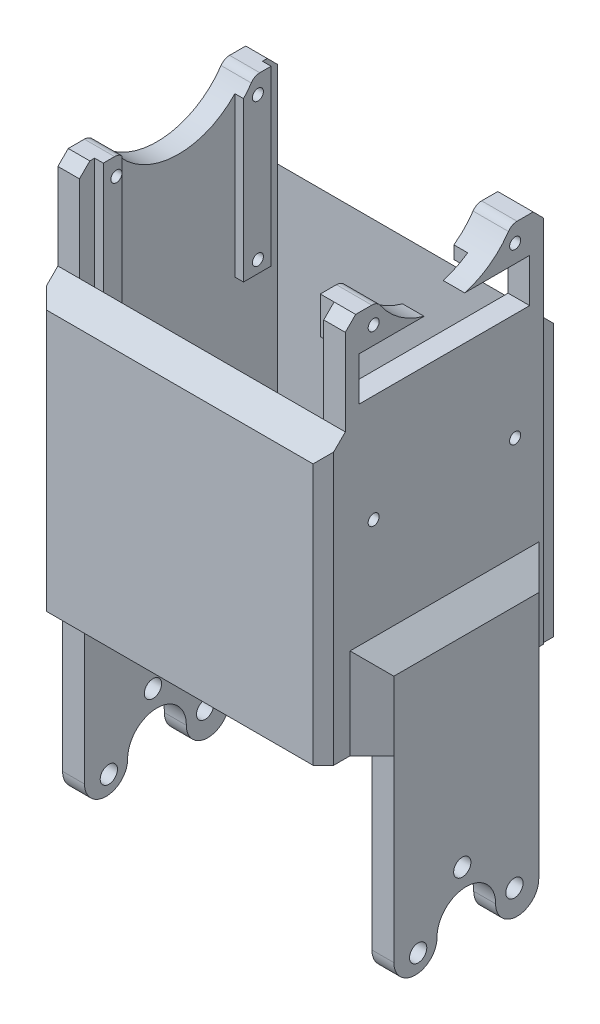
SolidWorks part; units mm, degrees
material "PLA"
ref_plane "Front Plane" through (0, 0, 0) normal (0, 0, 1) x (1, 0, 0)
ref_plane "Top Plane" through (0, 0, 0) normal (0, 1, 0) x (1, 0, 0)
ref_plane "Right Plane" through (0, 0, 0) normal (1, 0, 0) x (0, 0, -1)
sketch "Sketch1" plane through (0, 0, 0) normal (0, 0, 1) x (1, 0, 0)
  line L0 (0, 0) -> (35.4, 0)
  line L1 (35.4, 0) -> (35.4, 51.875)
  line L2 (0, 0) -> (-3.125, 0) construction
  line L3 (35.4, 0) -> (38.525, 0) construction
  line L4 (-3.125, -3.125) -> (38.525, -3.125)
  line L5 (38.525, -3.125) -> (38.525, 51.875)
  line L6 (-3.125, -3.125) -> (-3.125, 51.875)
  line L7 (0, 0) -> (0, 51.875)
  line L8 (0, 51.875) -> (-3.125, 51.875)
  line L9 (35.4, 51.875) -> (38.525, 51.875)
  dimension "D1" = 35.4
  dimension "D2" = 3.125
  dimension "D3" = 3.125
  dimension "D4" = 3.125
  dimension "D5" = 55
  dimension "D6" = 55
extrude "Boss-Extrude1" add sketch "Sketch1" along normal blind 28.72
sketch "Sketch2" plane through (38.525, 0, 0) normal (1, 0, 0) x (0, 0, -1)
  line L0 (-28.72, 46.285) -> (0, 46.285) construction
  line L1 (-28.72, -3.125) -> (-28.72, 51.875) construction
  line L2 (0, -3.125) -> (0, 51.875) construction
  line L3 (-28.72, 51.875) -> (0, 51.875) construction
  line L4 (-14.36, 46.285) -> (-14.36, 57.485) construction
  circle A0 centre (-14.36, 57.485) radius 11.2
  dimension "D1" = 5.59
  dimension "D2" = 11.2
extrude "Cut-Extrude1" cut sketch "Sketch2" against normal through all
fillet "Fillet2" radius 1.5 4 edges at (-1.5625, 51.875, 24.0537) (-1.5625, 51.875, 4.6663) (36.9625, 51.875, 4.6663) (36.9625, 51.875, 24.0537)
sketch "Sketch3" plane through (0, 0, 0) normal (0, 0, -1) x (-1, 0, 0)
  line L1 (-38.325, 37.875) -> (3.125, 37.875)
  line L2 (-38.325, 37.875) -> (-38.325, -3.125)
  line L3 (-38.325, -3.125) -> (3.125, -3.125)
  line L4 (3.125, 37.875) -> (3.125, -3.125)
extrude "Boss-Extrude2" add sketch "Sketch3" along normal blind 3.175
sketch "Sketch4" plane through (0, 0, 28.72) normal (0, 0, 1) x (1, 0, 0)
  line L1 (-3.125, 37.875) -> (38.525, 37.875)
  line L2 (-3.125, 37.875) -> (-3.125, -3.125)
  line L3 (-3.125, -3.125) -> (38.525, -3.125)
  line L4 (38.525, 37.875) -> (38.525, -3.125)
extrude "Boss-Extrude3" add sketch "Sketch4" along normal blind 3.175
chamfer "Chamfer1" distance 3.175 angle 45 2 edges at (17.6, 37.875, -3.175) (17.7, 37.875, 31.895)
chamfer "Chamfer2" distance 1.5 angle 45 4 edges at (-1.5625, 51.875, 0) (36.9625, 51.875, 0) (-1.5625, 51.875, 28.72) (36.9625, 51.875, 28.72)
chamfer "Chamfer3" distance 1.5 angle 45 4 edges at (-3.125, 15.7875, -3.175) (38.325, 15.7875, -3.175) (38.525, 15.7875, 31.895) (-3.125, 15.7875, 31.895)
sketch "Sketch5" plane through (0, 0, 0) normal (1, 0, 0) x (0, 0, -1)
  line L0 (-3.8368, 51.875) -> (-1.5, 51.875) construction
  line L2 (-2.2006, 51.875) -> (-2.2006, 26.7908)
  line L3 (-2.2006, 26.7908) -> (-6.2006, 26.7908)
  line L4 (-6.2006, 49.8127) -> (-6.2006, 26.7908)
  line L6 (-26.5194, 51.875) -> (-26.5194, 26.7908)
  line L7 (-26.5194, 26.7908) -> (-23.7797, 26.7908)
  line L8 (-23.7797, 51.4262) -> (-23.7797, 26.7908)
  line L9 (-27.22, 51.875) -> (-24.8832, 51.875) construction
  line L10 (-3.8368, 51.875) -> (-2.2006, 51.875)
  line L11 (-26.5194, 51.875) -> (-24.8832, 51.875)
  circle A0 centre (-24.61, 49.2608) radius 0.8
  circle A1 centre (-24.61, 28.5608) radius 0.8
  circle A2 centre (-4.11, 28.5608) radius 0.8
  circle A3 centre (-4.11, 49.2608) radius 0.8
  arc A4 (-3.8368, 51.875) -> (-5.0797, 51.2148) centre (-3.8368, 50.375) ccw construction
  arc A5 (-23.6403, 51.2148) -> (-5.0797, 51.2148) centre (-14.36, 57.485) ccw construction
  arc A6 (-23.6403, 51.2148) -> (-24.8832, 51.875) centre (-24.8832, 50.375) ccw construction
  arc A7 (-3.8368, 51.875) -> (-5.0797, 51.2148) centre (-3.8368, 50.375) ccw
  arc A8 (-23.6403, 51.2148) -> (-23.7797, 51.4262) centre (-14.36, 57.485) ccw
  arc A9 (-23.6403, 51.2148) -> (-24.8832, 51.875) centre (-24.8832, 50.375) ccw
  arc A10 (-6.2006, 49.8127) -> (-5.0797, 51.2148) centre (-14.36, 57.485) ccw
  line M8 (-1.5, 51.875) -> (-3.8368, 51.875)
  arc M9 (-3.8368, 51.875) -> (-5.0797, 51.2148) centre (-3.8368, 50.375) ccw
  arc M10 (-5.0797, 51.2148) -> (-23.6403, 51.2148) centre (-14.36, 57.485) cw
  arc M11 (-23.6403, 51.2148) -> (-24.8832, 51.875) centre (-24.8832, 50.375) ccw
  line M12 (-24.8832, 51.875) -> (-27.22, 51.875)
extrude "Boss-Extrude4" add sketch "Sketch5" along normal blind 1.25 contours L4 L3 L2 A3 A2 M10 M8 M9 | L8 L6 L7 A1 A0 M11 M12 region at (0, 39.3275, 25.186) region at (0, 39.1233, 4.1775)
sketch "Sketch6" plane through (0, 0, 0) normal (1, 0, 0) x (0, 0, -1)
  circle A0 centre (-24.61, 49.2608) radius 0.8
  circle A1 centre (-24.61, 28.5608) radius 0.8
  circle A2 centre (-4.11, 28.5608) radius 0.8
  circle A3 centre (-4.11, 49.2608) radius 0.8
extrude "Cut-Extrude2" cut sketch "Sketch6" against normal up to next
sketch "Sketch7" plane through (0, -3.125, 0) normal (0, -1, 0) x (1, 0, 0)
  line L0 (11.7, 22.36) -> (23.7, 22.36) construction
  line L1 (23.7, 22.36) -> (23.7, 6.36) construction
  line L2 (23.7, 6.36) -> (11.7, 6.36) construction
  line L3 (11.7, 6.36) -> (11.7, 22.36) construction
  line L6 (-3.125, 30.395) -> (-3.125, -1.675) construction
  line L7 (-1.625, 31.895) -> (37.025, 31.895) construction
  circle A0 centre (11.7, 22.36) radius 1.35
  circle A1 centre (23.7, 22.36) radius 1.35
  circle A2 centre (23.7, 6.36) radius 1.35
  circle A3 centre (11.7, 6.36) radius 1.35
  dimension "D1" = 2.7
  dimension "D2" = 2.7
  dimension "D3" = 2.7
  dimension "D4" = 2.7
  dimension "D5" = 14.825
  dimension "D6" = 9.535
extrude "Cut-Extrude3" cut sketch "Sketch7" against normal up to next
sketch "Sketch8" plane through (35.4, 0, 0) normal (-1, 0, 0) x (0, 0, 1)
  line L0 (7.86, 48.7133) -> (7.86, 45.9108) construction
  line L1 (1.5, 51.875) -> (5.0709, 51.875)
  line L2 (1.5, 51.875) -> (1.5, 46.5164)
  line L3 (1.5, 46.5164) -> (7.86, 46.5164)
  line L4 (7.86, 48.7133) -> (7.86, 46.5164)
  line L5 (20.86, 45.9108) -> (20.86, 48.7133) construction
  line L6 (20.86, 46.5164) -> (27.22, 46.5164)
  line L7 (20.86, 46.5164) -> (20.86, 48.7133)
  line L8 (23.6491, 51.875) -> (27.22, 51.875)
  line L9 (27.22, 46.5164) -> (27.22, 51.875)
  line L10 (28.72, 0) -> (28.72, 37.875) construction
  line L11 (28.72, 27.0608) -> (0, 27.0608)
  line L12 (28.72, 27.0608) -> (28.72, 22.5608)
  line L13 (28.72, 22.5608) -> (0, 22.5608)
  line L14 (0, 27.0608) -> (0, 22.5608)
  circle A0 centre (24.61, 49.2608) radius 0.8
  circle A1 centre (4.11, 49.2608) radius 0.8
  circle A2 centre (4.11, 24.8108) radius 0.8
  circle A3 centre (24.61, 24.735) radius 0.8758
  arc A4 (5.0077, 51.9796) -> (7.7768, 48.8846) centre (14.36, 57.5608) ccw construction
  arc A5 (5.0709, 51.875) -> (7.7768, 48.8846) centre (14.36, 57.5608) ccw
  arc A6 (20.9432, 48.8846) -> (23.7123, 51.9796) centre (14.36, 57.5608) ccw construction
  arc A7 (20.9432, 48.8846) -> (23.6491, 51.875) centre (14.36, 57.5608) ccw
  spline S0 degree 3 poles (-1990.0282, 140.523) (-63.2874, 38.9164) (7.1505, 51.8916) (8.5344, 45.7425) (-54.2619, 48.1267) (797.0615, -1788.4088) knots -94.086847 -94.086847 -94.086847 -94.086847 0.333333 0.666667 91.791331 91.791331 91.791331 91.791331 weights 1 1 1 1 1 1 only from (7.8374, 48.8108) to (7.86, 48.7133) construction
  spline S1 degree 3 poles (-490.8158, 1985.2839) (-30.2177, -10.261) (5.7924, 51.2853) (9.6673, 46.6143) (-37.1403, 7.4582) (460.9115, -1898.6662) knots -96.396237 -96.396237 -96.396237 -96.396237 0.333333 0.666667 89.616596 89.616596 89.616596 89.616596 weights 1 1 1 1 1 1 only from (7.7768, 48.8846) to (7.8374, 48.8108) construction
  spline S2 degree 3 poles (7.8374, 48.8108) (7.8425, 48.8003) (7.851, 48.7791) (7.8584, 48.746) (7.86, 48.7242) (7.86, 48.7133) knots 0 0 0 0 0.333333 0.666667 1 1 1 1 weights 1 1 1 1 1 1
  spline S3 degree 3 poles (7.7768, 48.8846) (7.785, 48.8784) (7.8005, 48.8647) (7.8213, 48.8396) (7.8325, 48.8208) (7.8374, 48.8108) knots 0 0 0 0 0.333333 0.666667 1 1 1 1 weights 1 1 1 1 1 1
  spline S4 degree 3 poles (356.7329, 2019.8863) (65.3071, 28.7044) (19.6993, 46.3936) (21.999, 51.095) (61.1419, 27.6757) (-1071.4379, -1626.044) knots -39.976297 -39.976297 -39.976297 -39.976297 0.341381 0.67758 38.768425 38.768425 38.768425 38.768425 weights 1 1 1 1 1 1 only from (20.86, 48.7133) to (20.9432, 48.8846) construction
  spline S5 degree 3 poles (20.86, 48.7133) (20.86, 48.7357) (20.8668, 48.7804) (20.896, 48.8401) (20.9264, 48.8718) (20.9432, 48.8846) knots 0 0 0 0 0.341381 0.67758 1 1 1 1 weights 1 1 1 1 1 1
  point P42 (0, 24.8108)
  line M9 (0, 37.875) -> (0, 0)
  line M11 (28.72, 0) -> (28.72, 37.875)
  line M14 (27.22, 51.875) -> (24.8832, 51.875)
  arc M15 (24.8832, 51.875) -> (23.6403, 51.2148) centre (24.8832, 50.375) ccw
  arc M16 (23.6403, 51.2148) -> (5.0797, 51.2148) centre (14.36, 57.485) cw
  arc M17 (5.0797, 51.2148) -> (3.8368, 51.875) centre (3.8368, 50.375) ccw
  line M18 (3.8368, 51.875) -> (1.5, 51.875)
  dimension "D1" = 4.5
extrude "Boss-Extrude5" add sketch "Sketch8" along normal blind 2 contours L6 L9 L7 A0 M14 M15 M16 | L4 L2 L3 A1 M16 M17 M18 | L13 L11 A3 A2 M11 M9 region at (35.4, 49.6068, 22.4374) region at (35.4, 51.7918, 2.6684) region at (35.4, 24.8122, 14.3273)
sketch "Sketch9" plane through (35.4, 0, 0) normal (-1, 0, 0) x (0, 0, 1)
  line L0 (24.61, 50.0607) -> (24.61, 48.4608) construction
  line L1 (4.11, 50.0607) -> (4.11, 48.4608) construction
  line L2 (4.11, 25.6107) -> (4.11, 24.0108) construction
  line L3 (24.61, 25.6107) -> (24.61, 24.0108) construction
  line L4 (26.72, 24.4506) -> (26.72, 51.0993) construction
  line L5 (26.72, 46.6769) -> (2, 46.6769)
  line L6 (26.72, 46.6769) -> (26.72, 40.3691)
  line L7 (26.72, 40.3691) -> (2, 40.3691)
  line L8 (2, 46.6769) -> (2, 40.3691)
  line L9 (2, 51.0993) -> (2, 24.4506) construction
  circle A0 centre (24.61, 24.8107) radius 0.8
  circle A1 centre (4.11, 24.8107) radius 0.8
  circle A2 centre (4.11, 49.2607) radius 0.8
  circle A3 centre (24.61, 49.2607) radius 0.8
extrude "Cut-Extrude4" cut sketch "Sketch9" against normal up to next
sketch "Sketch10" plane through (-3.125, 0, 0) normal (-1, 0, 0) x (0, 0, 1)
  line L0 (3.86, -9.6264) -> (3.86, 3.5377) construction
  line L1 (3.86, -29.0691) -> (3.86, -5.125) construction
  line L2 (24.86, -9.6264) -> (24.86, 3.5377) construction
  line L3 (24.86, -29.0691) -> (24.86, -5.125) construction
  line L4 (30.395, -3.125) -> (-1.675, -3.125) construction
  line L5 (3.86, 6.875) -> (24.86, 6.875)
  line L6 (3.86, 6.875) -> (3.86, -29.0691)
  line L8 (24.86, 6.875) -> (24.86, -29.0691)
  spline S0 degree 3 poles (6.1384, -28.3409) (6.0777, -29.0707) (6.5507, -29.6296) (7.2805, -29.6903) knots 0 0 0 0 1 1 1 1 weights 1 0.804738 0.804738 1 construction
  spline S1 degree 3 poles (6.1384, -28.3409) (6.2469, -27.0371) (7.493, -26.6384) (8.3382, -27.637) (9.1835, -28.6357) (8.5843, -29.7988) (7.2805, -29.6903) knots 0 0 0 0 0.5 0.5 0.5 1 1 1 1 weights 1 0.588456 0.588456 1 0.588456 0.588456 1 construction
  spline S2 degree 3 poles (15.0441, -20.8034) (14.3143, -20.7427) (13.7554, -21.2157) (13.6947, -21.9455) knots 0 0 0 0 1 1 1 1 weights 1 0.804738 0.804738 1 construction
  spline S3 degree 3 poles (15.0441, -20.8034) (16.3479, -20.9119) (16.7466, -22.158) (15.748, -23.0032) (14.7493, -23.8485) (13.5862, -23.2493) (13.6947, -21.9455) knots 0 0 0 0 0.5 0.5 0.5 1 1 1 1 weights 1 0.588456 0.588456 1 0.588456 0.588456 1 construction
  spline S4 degree 3 poles (22.5816, -29.7091) (22.6423, -28.9793) (22.1693, -28.4204) (21.4395, -28.3597) knots 0 0 0 0 1 1 1 1 weights 1 0.804738 0.804738 1 construction
  spline S5 degree 3 poles (22.5816, -29.7091) (22.4731, -31.0129) (21.227, -31.4116) (20.3818, -30.413) (19.5365, -29.4143) (20.1357, -28.2512) (21.4395, -28.3597) knots 0 0 0 0 0.5 0.5 0.5 1 1 1 1 weights 1 0.588456 0.588456 1 0.588456 0.588456 1 construction
  spline S6 degree 3 poles (18.6098, -29.0691) (18.6098, -35.3193) (24.86, -35.3193) (24.86, -29.0691) knots 0 0 0 0 1 1 1 1 weights 1 0.333333 0.333333 1 construction
  spline S7 degree 3 poles (10.1102, -29.0691) (10.0842, -26.5591) (11.8499, -24.775) (14.36, -24.775) (16.8701, -24.775) (18.6358, -26.5591) (18.6098, -29.0691) knots 0 0 0 0 0.5 0.5 0.5 1 1 1 1 weights 1 0.802287 0.802287 1 0.802287 0.802287 1 construction
  spline S8 degree 3 poles (3.86, -29.0691) (3.86, -30.8997) (5.1545, -32.1942) (6.9851, -32.1942) (8.8158, -32.1942) (10.1102, -30.8997) (10.1102, -29.0691) knots 0 0 0 0 0.5 0.5 0.5 1 1 1 1 weights 1 0.804738 0.804738 1 0.804738 0.804738 1 construction
  spline S9 degree 3 poles (6.1384, -28.3409) (6.0777, -29.0707) (6.5507, -29.6296) (7.2805, -29.6903) knots 0 0 0 0 1 1 1 1 weights 1 0.804738 0.804738 1
  spline S10 degree 3 poles (6.1384, -28.3409) (6.2469, -27.0371) (7.493, -26.6384) (8.3382, -27.637) (9.1835, -28.6357) (8.5843, -29.7988) (7.2805, -29.6903) knots 0 0 0 0 0.5 0.5 0.5 1 1 1 1 weights 1 0.588456 0.588456 1 0.588456 0.588456 1
  spline S11 degree 3 poles (15.0441, -20.8034) (14.3143, -20.7427) (13.7554, -21.2157) (13.6947, -21.9455) knots 0 0 0 0 1 1 1 1 weights 1 0.804738 0.804738 1
  spline S12 degree 3 poles (15.0441, -20.8034) (16.3479, -20.9119) (16.7466, -22.158) (15.748, -23.0032) (14.7493, -23.8485) (13.5862, -23.2493) (13.6947, -21.9455) knots 0 0 0 0 0.5 0.5 0.5 1 1 1 1 weights 1 0.588456 0.588456 1 0.588456 0.588456 1
  spline S13 degree 3 poles (22.5816, -29.7091) (22.6423, -28.9793) (22.1693, -28.4204) (21.4395, -28.3597) knots 0 0 0 0 1 1 1 1 weights 1 0.804738 0.804738 1
  spline S14 degree 3 poles (22.5816, -29.7091) (22.4731, -31.0129) (21.227, -31.4116) (20.3818, -30.413) (19.5365, -29.4143) (20.1357, -28.2512) (21.4395, -28.3597) knots 0 0 0 0 0.5 0.5 0.5 1 1 1 1 weights 1 0.588456 0.588456 1 0.588456 0.588456 1
  spline S15 degree 3 poles (18.6098, -29.0691) (18.6098, -35.3193) (24.86, -35.3193) (24.86, -29.0691) knots 0 0 0 0 1 1 1 1 weights 1 0.333333 0.333333 1
  spline S16 degree 3 poles (10.1102, -29.0691) (10.0842, -26.5591) (11.8499, -24.775) (14.36, -24.775) (16.8701, -24.775) (18.6358, -26.5591) (18.6098, -29.0691) knots 0 0 0 0 0.5 0.5 0.5 1 1 1 1 weights 1 0.802287 0.802287 1 0.802287 0.802287 1
  spline S17 degree 3 poles (3.86, -29.0691) (3.86, -30.8997) (5.1545, -32.1942) (6.9851, -32.1942) (8.8158, -32.1942) (10.1102, -30.8997) (10.1102, -29.0691) knots 0 0 0 0 0.5 0.5 0.5 1 1 1 1 weights 1 0.804738 0.804738 1 0.804738 0.804738 1
  dimension "D1" = 10
extrude "Boss-Extrude6" add sketch "Sketch10" along normal blind 3.175
chamfer "Chamfer8" distance 3.175 angle 45 3 edges at (-3.125, 1.875, 3.86) (-3.125, 6.875, 14.36) (-3.125, 1.875, 24.86)
ref_plane "Plane1" through (17.7, 0, 0) normal (1, 0, 0) x (0, 0, -1)
mirror "Mirror2" about plane through (17.7, 0, 0) normal (1, 0, 0) of "Boss-Extrude6"
chamfer "Chamfer9" distance 3.175 angle 45 3 edges at (38.525, 1.875, 24.86) (38.525, 6.875, 14.36) (38.525, 1.875, 3.86)
